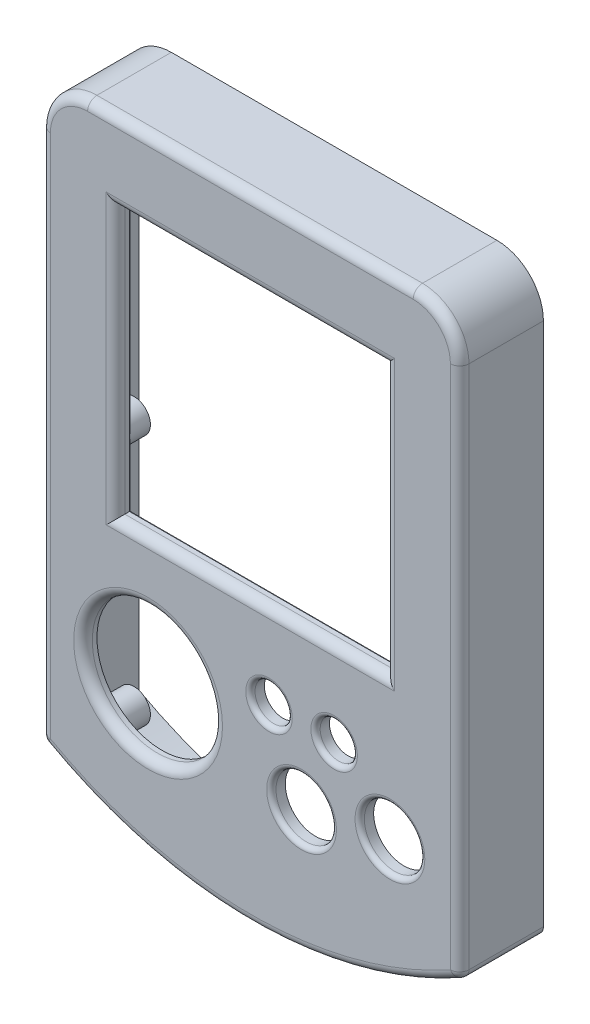
SolidWorks part; units mm, degrees
ref_plane "前视基准面" through (0, 0, 0) normal (0, 0, 1) x (1, 0, 0)
ref_plane "上视基准面" through (0, 0, 0) normal (0, 1, 0) x (1, 0, 0)
ref_plane "右视基准面" through (0, 0, 0) normal (1, 0, 0) x (0, 0, -1)
sketch "草图1" plane through (0, 0, 0) normal (0, 0, 1) x (1, 0, 0)
  line L1 (-40, 68) -> (-5, 68)
  line L2 (-45, 63) -> (-45, 0)
  line L3 (-45, 0) -> (0, 0)
  line L4 (0, 63) -> (0, 0)
  arc A0 (-5, 68) -> (0, 63) centre (-5, 63) cw
  arc A1 (-40, 68) -> (-45, 63) centre (-40, 63) ccw
  point P7 (0, 68)
  point P10 (-45, 68)
  dimension "D3" = 5
  dimension "D4" = 5
  dimension "D1" = 45
  dimension "D2" = 68
extrude "凸台-拉伸1" add sketch "草图1" along normal blind 9 contours L1 A0 L4 L3 L2 A1
sketch "草图3" plane through (0, 0, 0) normal (0, 0, -1) x (-1, 0, 0)
  line L0 (22.5, 0) -> (22.5, 50000) construction
  line L2 (0, 63) -> (0, 0) construction
  line L4 (45, 6) -> (45, 0)
  line L5 (45, 0) -> (0, 0)
  line L6 (0, 0) -> (0, 6)
  line L7 (0, 63) -> (0, 0) construction
  line L8 (45, 63) -> (45, 0) construction
  arc A0 (0, 6) -> (45, 6) centre (22.5, 45.1875) ccw
  point P7 (45, 6)
  line M3 (45, 0) -> (45, 63)
  line M5 (0, 63) -> (0, 0)
  line M6 (0, 0) -> (45, 0)
  dimension "D1" = 6
extrude "切除-拉伸2" cut sketch "草图3" against normal through all contours A0 L5 M3 | A0 M5 M6 region at (-5.5476, 1.7775, 0) region at (-39.4524, 1.7775, 0)
shell "抽壳2" thickness 1.5 removed face at (-22.5, 45.0118, 0)
sketch "草图4" plane through (0, 0, 0) normal (0, 0, -1) x (-1, 0, 0)
  line L0 (22.5, 68.5) -> (22.5, 50068.5) construction
  line L1 (8, 59.5) -> (37, 59.5)
  line L2 (8, 59.5) -> (8, 30.5)
  line L3 (8, 30.5) -> (37, 30.5)
  line L4 (37, 59.5) -> (37, 30.5)
  line L5 (40, 66.5) -> (5, 66.5) construction
  line L6 (40, 68) -> (5, 68) construction
  line L7 (45, 63) -> (45, 6) construction
  line L8 (0, 63) -> (0, 6) construction
  circle A0 centre (33.5, 17) radius 7
  circle A1 centre (7.5, 15.5) radius 3.25
  circle A2 centre (17, 13.5) radius 3.25
  circle A3 centre (13.5, 21.5) radius 2
  circle A4 centre (20.5, 21.5) radius 2
  point P8 (22.5, 66.5)
  dimension "D4" = 14
  dimension "D7" = 6.5
  dimension "D8" = 6.5
  dimension "D13" = 4
  dimension "D14" = 4
  dimension "D1" = 29
  dimension "D2" = 29
  dimension "D3" = 8.5
  dimension "D5" = 11.5
  dimension "D6" = 51
  dimension "D9" = 7.5
  dimension "D10" = 17
  dimension "D11" = 52.5
  dimension "D12" = 54.5
  dimension "D15" = 46.5
  dimension "D16" = 7
  dimension "D17" = 13.5
extrude "切除-拉伸3" cut sketch "草图4" against normal through all
fillet "圆角1" radius 1 4 edges at (-22.5, 59.5, 9) (-8, 45, 9) (-22.5, 30.5, 9) (-37, 45, 9)
fillet "圆角2" radius 1 1 edges at (-40.5, 17, 9)
fillet "圆角3" radius 0.5 4 edges at (-15.5, 21.5, 9) (-22.5, 21.5, 9) (-10.75, 15.5, 9) (-20.25, 13.5, 9)
fillet "圆角5" radius 1 2 edges at (0, 6, 4.5) (-45, 6, 4.5)
fillet "圆角7" radius 1 8 edges at (-0.1379, 6.0766, 9) (-44.8621, 6.0766, 9) (-22.5, 0, 9) (-45, 34.7916, 9) (-43.5355, 66.5355, 9) (0, 34.7916, 9) (-1.4645, 66.5355, 9) (-22.5, 68, 9)
sketch "草图5" plane through (0, 0, 7.5) normal (0, 0, -1) x (-1, 0, 0)
  line L1 (6.65, 64.75) -> (38.35, 64.75)
  line L2 (6.65, 64.75) -> (6.65, 29.15)
  line L3 (6.65, 29.15) -> (38.35, 29.15)
  line L4 (38.35, 64.75) -> (38.35, 29.15)
  line L6 (22.5, 55.8413) -> (22.5, 50055.8413) construction
  line L7 (8, 30.5) -> (8, 59.5) construction
  line L8 (37, 59.5) -> (37, 30.5) construction
  line L9 (37, 30.5) -> (8, 30.5) construction
  line L10 (39.35, 65.75) -> (39.35, 28.15)
  line L11 (5.65, 28.15) -> (39.35, 28.15)
  line L12 (5.65, 65.75) -> (5.65, 28.15)
  line L13 (5.65, 65.75) -> (39.35, 65.75)
  dimension "D1" = 31.7
  dimension "D2" = 35.6
  dimension "D3" = 1.35
  dimension "D4" = 1
extrude "凸台-拉伸2" add sketch "草图5" along normal blind 1.4
sketch "草图6" plane through (0, 0, 7.5) normal (0, 0, -1) x (-1, 0, 0)
  line L0 (40, 68) -> (5, 68) construction
  line L1 (0, 63) -> (0, 6.5833) construction
  line L2 (4.8, 63) -> (4.8, 36) construction
  line L3 (22.5, -955.0295) -> (22.5, 49044.9705) construction
  line L4 (45, 63) -> (45, 6.5833) construction
  circle A0 centre (4.8, 63) radius 1.75
  circle A1 centre (4.8, 63) radius 0.75
  circle A2 centre (4.8, 36) radius 1.75
  circle A3 centre (4.8, 36) radius 0.75
  circle A4 centre (4.8, 9) radius 1.75
  circle A5 centre (4.8, 9) radius 0.75
  circle A6 centre (40.2, 9) radius 0.75
  circle A7 centre (40.2, 9) radius 1.75
  circle A8 centre (40.2, 36) radius 0.75
  circle A9 centre (40.2, 36) radius 1.75
  circle A10 centre (40.2, 63) radius 0.75
  circle A11 centre (40.2, 63) radius 1.75
  dimension "D1" = 3.5
  dimension "D4" = 1
  dimension "D2" = 5
  dimension "D3" = 4.8
  dimension "D6" = 27
  dimension "D5" = 3
extrude "凸台-拉伸3" add sketch "草图6" along normal blind 3.7
